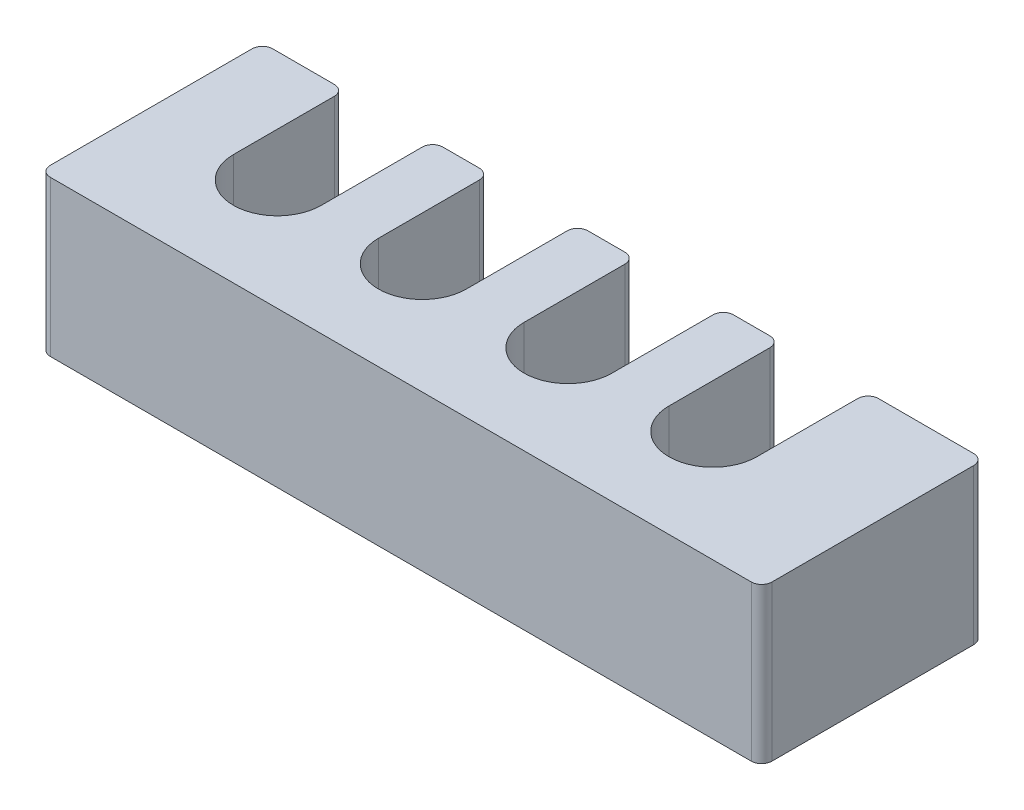
SolidWorks part; units mm, degrees
ref_plane "Ebene vorne" through (0, 0, 0) normal (0, 0, 1) x (1, 0, 0)
ref_plane "Ebene oben" through (0, 0, 0) normal (0, 1, 0) x (1, 0, 0)
ref_plane "Ebene rechts" through (0, 0, 0) normal (1, 0, 0) x (0, 0, -1)
sketch "Skizze1" plane through (0, 0, 0) normal (0, 1, 0) x (1, 0, 0)
  line L1 (0, 0) -> (139.5, 0)
  line L2 (0, 0) -> (0, 58)
  line L3 (0, 58) -> (139.5, 58)
  line L4 (139.5, 0) -> (139.5, 58)
  dimension "D1" = 139.5
  dimension "D2" = 58
extrude "Aufsatz-Linear austragen1" add sketch "Skizze1" along normal blind 28
sketch "Skizze4" plane through (0, 0, -58) normal (0, 0, -1) x (-1, 0, 0)
  line L0 (-52.43, 28) -> (-52.43, -7.154) construction
  line L1 (-3.63, 0) -> (-80.58, 0)
  line L5 (-32.9, 28) -> (-15.9, 28)
  line L6 (-32.9, 28) -> (-32.9, 4)
  line L8 (-15.9, 28) -> (-15.9, 4)
  line L9 (-60.93, 28) -> (-43.93, 28)
  line L10 (-60.93, 28) -> (-60.93, 4)
  line L12 (-43.93, 28) -> (-43.93, 4)
  line L13 (-89.08, 28) -> (-72.08, 28)
  line L14 (-89.08, 28) -> (-89.08, 4)
  line L16 (-72.08, 28) -> (-72.08, 4)
  line L17 (-24.4, 28) -> (-24.4, -7.154) construction
  line L18 (-80.58, 28) -> (-80.58, -7.154) construction
  line L19 (-108.58, 28) -> (-108.58, -7.154) construction
  line L20 (-139.5, 0) -> (0, 0) construction
  line L22 (-72.08, 4) -> (-60.93, 4)
  line L23 (-43.93, 4) -> (-32.9, 4)
  line L24 (-139.5, 28) -> (0, 28) construction
  line L25 (-139.5, 28) -> (0, 28) construction
  line L27 (-3.63, 0) -> (-5, 0)
  line L29 (-5, 4) -> (-15.9, 4)
  line L30 (-108.58, 28) -> (-100.08, 28)
  line L31 (-100.08, 28) -> (-100.08, 4)
  line L35 (-134.5, 4) -> (-117.08, 4)
  line L36 (-117.08, 4) -> (-117.08, 28)
  line L37 (-117.08, 28) -> (-108.58, 28)
  line L38 (-89.08, 4) -> (-100.08, 4)
  line L39 (-134.5, 0) -> (-80.58, 0)
  line L41 (-5, 4) -> (-5, 0)
  line L42 (-134.5, 0) -> (-134.5, 4)
  line L43 (-139.5, 28) -> (-139.5, 0) construction
  dimension "D2" = 17
  dimension "D3" = 17
  dimension "D4" = 28.03
  dimension "D5" = 28.15
  dimension "D6" = 17
  dimension "D7" = 4
  dimension "D8" = 19.4
  dimension "D10" = 28
  dimension "D11" = 17
  dimension "D12" = 5
  dimension "D13" = 5
extrude "Schnitt-Linear austragen2" cut sketch "Skizze4" against normal blind 30
fillet "Verrundung1" radius 8.5 8 edges at (15.9, 16, -28) (32.9, 16, -28) (43.93, 16, -28) (60.93, 16, -28) (72.08, 16, -28) (89.08, 16, -28) (100.08, 16, -28) (117.08, 16, -28)
sketch "Skizze5" plane through (0, 4, 0) normal (0, -1, 0) x (1, 0, 0)
  line L0 (94.58, -58) -> (94.58, -28) construction
  line L1 (89.08, -58) -> (100.08, -58) construction
  line L2 (80.58, -28) -> (108.58, -28) construction
  line L3 (66.505, -58) -> (66.505, -28) construction
  line L4 (72.08, -58) -> (60.93, -58) construction
  line L5 (80.58, -28) -> (52.43, -28) construction
  line L6 (38.415, -58) -> (38.415, -28) construction
  line L7 (43.93, -58) -> (32.9, -58) construction
  line L8 (52.43, -28) -> (24.4, -28) construction
  line L9 (12.28, -58) -> (5, -58)
  line L10 (134.5, -58) -> (117.08, -58) construction
  line L11 (134.5, -28) -> (5, -28) construction
  line L13 (5, -58) -> (5, -28)
  line L14 (80.58, -28) -> (80.58, -70) construction
  line L15 (96.58, -28) -> (92.58, -28)
  line L16 (96.58, -28) -> (96.58, -58)
  line L17 (96.58, -58) -> (92.58, -58)
  line L18 (92.58, -28) -> (92.58, -58)
  line L19 (68.58, -28) -> (64.43, -28)
  line L20 (68.58, -28) -> (68.58, -58)
  line L21 (68.58, -58) -> (64.43, -58)
  line L22 (64.43, -28) -> (64.43, -58)
  line L23 (40.43, -28) -> (36.28, -28)
  line L24 (134.5, -28) -> (120.58, -28)
  line L26 (134.5, -58) -> (120.58, -58)
  line L27 (120.58, -28) -> (120.58, -58)
  line L28 (40.43, -28) -> (40.43, -58)
  line L29 (40.43, -58) -> (36.28, -58)
  line L30 (36.28, -28) -> (36.28, -58)
  line L32 (12.28, -28) -> (12.28, -58)
  line L35 (8.13, -28) -> (8.13, -58) [skipped]
  line L37 (134.5, -28) -> (134.5, -58) construction
  line L38 (134.5, -28) -> (134.5, -58) construction
  line L39 (134.5, -28) -> (134.5, -58)
  line L40 (5, -28) -> (12.28, -28)
  line L41 (12.28, -58) -> (8.13, -58) [skipped]
  line L42 (12.28, -28) -> (8.13, -28) [skipped]
  dimension "D1" = 24
  dimension "D3" = 24
  dimension "D5" = 24
  dimension "D4" = 3
extrude "Aufsatz-Linear austragen2" add sketch "Skizze5" along normal up to surface (4 mm away) up to face at (69.75, 0, -36)
fillet "Verrundung2" radius 5 8 edges at (12.28, 2, -28) (36.28, 2, -28) (40.43, 2, -28) (64.43, 2, -28) (92.58, 2, -28) (68.58, 2, -28) (96.58, 2, -28) (120.58, 2, -28)
sketch "Skizze6" plane through (0, 0, 0) normal (0, -1, 0) x (1, 0, 0)
  line L0 (139.5, -58) -> (134.5, -58)
  line L1 (139.5, -58) -> (120.58, -58) construction
  line L2 (134.5, -58) -> (134.5, -43)
  line L3 (124.5, -25) -> (15, -25)
  line L4 (5, -43) -> (5, -58)
  line L6 (12.28, -58) -> (0, -58) construction
  line L7 (5, -58) -> (0, -58)
  line L8 (0, -58) -> (0, 0)
  line L9 (0, 0) -> (139.5, 0)
  line L10 (139.5, 0) -> (139.5, -58)
  line L11 (134.5, -43) -> (135.9783, -40.4394)
  line L12 (136.5, -38.4926) -> (136.5, -28)
  line L13 (131.5, -23) -> (129.0074, -23)
  line L14 (127.0606, -23.5217) -> (124.5, -25)
  line L16 (69.75, 0) -> (69.75, -87.8089) construction
  line L17 (12.4394, -23.5217) -> (15, -25)
  line L18 (8, -23) -> (10.4926, -23)
  line L19 (3, -38.4926) -> (3, -28)
  line L20 (5, -43) -> (3.5217, -40.4394)
  arc A2 (129.0074, -23) -> (127.0606, -23.5217) centre (129.0074, -26.8937) ccw
  arc A3 (135.9783, -40.4394) -> (136.5, -38.4926) centre (132.6063, -38.4926) ccw
  arc A4 (3.5217, -40.4394) -> (3, -38.4926) centre (6.8937, -38.4926) cw
  arc A5 (10.4926, -23) -> (12.4394, -23.5217) centre (10.4926, -26.8937) cw
  arc A6 (8, -23) -> (3, -28) centre (8, -28) ccw
  arc A7 (136.5, -28) -> (131.5, -23) centre (131.5, -28) ccw
  point P36 (3, -23)
  point P39 (136.5, -23)
  dimension "D4" = 15
  dimension "D10" = 3.8937
  dimension "D12" = 5
  dimension "D1" = 5
  dimension "D2" = 5
  dimension "D3" = 25
  dimension "D5" = 2
  dimension "D6" = 2
  dimension "D7" = 15
  dimension "D8" = 30
  dimension "D9" = 30
  dimension "D11" = 30
extrude "Aufsatz-Linear austragen3" add sketch "Skizze6" along normal blind 2
fillet "Verrundung3" radius 2 12 edges at (117.08, 16, -58) (100.08, 16, -58) (72.08, 16, -58) (43.93, 16, -58) (15.9, 16, -58) (32.9, 16, -58) (60.93, 16, -58) (89.08, 16, -58) (0, 13, -58) (139.5, 13, -58) (139.5, 13, 0) (0, 13, 0)
fillet "Verrundung4" radius 2 10 edges at (5, -1, -58) (12.28, 2, -58) (36.28, 2, -58) (40.43, 2, -58) (64.43, 2, -58) (68.58, 2, -58) (92.58, 2, -58) (96.58, 2, -58) (120.58, 2, -58) (134.5, -1, -58)
sketch "Skizze7" plane through (0, 28, 0) normal (0, 1, 0) x (1, 0, 0)
  line L0 (139.5, 2) -> (139.5, 56) construction
  line L1 (139.5, 15) -> (0, 15)
  line L2 (139.5, 15) -> (139.5, 0)
  line L3 (139.5, 0) -> (0, 0)
  line L4 (0, 15) -> (0, 0)
  dimension "D1" = 15
extrude "Schnitt-Linear austragen5" cut sketch "Skizze7" against normal through all
fillet "Verrundung5" radius 2 2 edges at (0, 13, -15) (139.5, 13, -15)
hole_wizard "M2.5 Gewindebohrung1" positions "Skizze8" profile "Skizze9" tap size "M2.5" standard "DIN"
sketch "Skizze8" plane through (0, 0, 0) normal (0, -1, 0) x (-1, 0, 0)
  line L0 (-15, 25) -> (-124.5, 25) construction
  line L1 (-134.5, 43) -> (-134.5, 56) construction
  line L2 (-5, 56) -> (-5, 43) construction
  line L4 (-15, 25) -> (-124.5, 25) construction
  point P0 (-130.75, 32.3)
  point P2 (-8.75, 32.3)
  point P13 (-8.75, 28.6562)
  dimension "D1" = 7.3
  dimension "D2" = 3.75
  dimension "D3" = 3.75
  dimension "D4" = 7.3
sketch "Skizze9" plane through (130.75, 0, -32.3) normal (1, 0, 0) x (0, 0, -1)
  line L0 (0, 0) -> (0, 4.8659)
  line L1 (0, 4.8659) -> (1.025, 4.25)
  line L2 (1.025, 4.25) -> (1.025, 0.25)
  line L3 (1.025, 0.25) -> (1.275, 0)
  line L5 (1.275, 0) -> (0, 0)
  line L6 (-1.025, 0.25) -> (-1.275, 0) construction
  line L10 (0, 4.8659) -> (-1.025, 4.25) construction
  line L11 (0, -6.35) -> (0, 107.95) construction
  dimension "Bohrerdurchmesser" = 2.05
  dimension "Bohrungstiefe" = 4.25
  dimension "Senkdurchmesser (Oben)" = 2.55
  dimension "Senkwinkel (Oben)" = 90
  dimension "Spitzenwinkel" = 118
cosmetic thread "Bohrungsgewinde1" parameters "D1"=5, "D2"=2.5
cosmetic thread "Bohrungsgewinde2" parameters "D1"=5, "D2"=2.5
